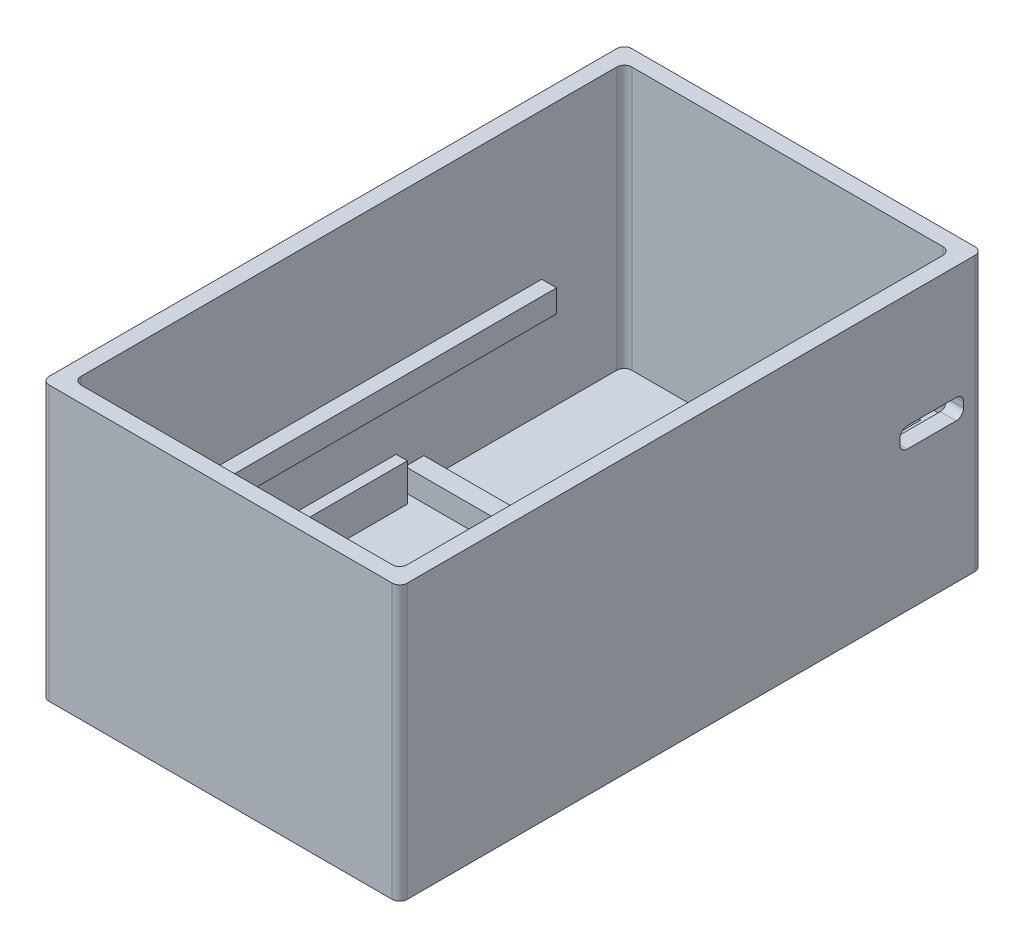
SolidWorks part; units mm, degrees
ref_plane "Front Plane" through (0, 0, 0) normal (0, 0, 1) x (1, 0, 0)
ref_plane "Top Plane" through (0, 0, 0) normal (0, 1, 0) x (1, 0, 0)
ref_plane "Right Plane" through (0, 0, 0) normal (1, 0, 0) x (0, 0, -1)
sketch "PCB Dimensions" plane through (0, 0, 0) normal (0, 1, 0) x (1, 0, 0)
  line L0 (0, 0) -> (-3.5355, 3.5355)
  line L1 (0, 0) -> (40.6457, 0)
  line L2 (0, 0) -> (0, -70.5657)
  line L3 (0, -70.5657) -> (40.6457, -70.5657)
  line L4 (40.6457, 0) -> (40.6457, -70.5657)
  line L5 (40.6457, -70.5657) -> (44.1812, -74.1012)
  line L6 (40.6457, 0) -> (44.1812, 3.5355)
  line L11 (0, -70.5657) -> (-3.5355, -74.1012)
  line L12 (44.1812, -74.1012) -> (-3.5355, -74.1012)
  line L13 (44.1812, -74.1012) -> (44.1812, 3.5355)
  line L14 (44.1812, 3.5355) -> (-3.5355, 3.5355)
  line L15 (-3.5355, -74.1012) -> (-3.5355, 3.5355)
extrude "Boss-Extrude3" add sketch "PCB Dimensions" along normal blind 1.5 contours L14 L15 L12 L13
sketch "Sketch5" plane through (0, 1.5, 0) normal (0, 1, 0) x (1, 0, 0)
  line L0 (-3.5355, 3.5355) -> (-1.4142, 1.4142)
  line L1 (-3.5355, 3.5355) -> (44.1812, 3.5355)
  line L2 (-3.5355, 3.5355) -> (-3.5355, -74.1012)
  line L7 (-3.5355, -74.1012) -> (44.1812, -74.1012)
  line L8 (44.1812, 3.5355) -> (44.1812, -74.1012)
  line L9 (44.1812, -74.1012) -> (42.0599, -71.9799)
  line L11 (-1.4142, 1.4142) -> (42.0599, 1.4142)
  line L12 (-1.4142, 1.4142) -> (-1.4142, -71.9799)
  line L13 (-1.4142, -71.9799) -> (42.0599, -71.9799)
  line L14 (42.0599, 1.4142) -> (42.0599, -71.9799)
extrude "Boss-Extrude5" add sketch "Sketch5" along normal blind 35 contours L14 L13 | L2 L7 L8 L1 region at (20.3228, 1.5, 35.2828)
fillet "Fillet1" radius 1 8 edges at (42.0599, 19, 71.9799) (-3.5355, 18.25, 74.1012) (44.1812, 18.25, 74.1012) (44.1812, 18.25, -3.5355) (-3.5355, 18.25, -3.5355) (-1.4142, 19, 71.9799) (42.0599, 19, -1.4142) (-1.4142, 19, -1.4142)
sketch "Sketch9" plane through (0, 1.5, 0) normal (0, 1, 0) x (1, 0, 0)
  line L3 (0.0799, -70.9799) -> (-1.8581, -70.9799)
  line L9 (0.0799, -28.9799) -> (-1.8581, -28.9799)
  line L10 (-1.8581, -70.9799) -> (-1.8581, -28.9799)
  line L15 (42.5038, -70.9799) -> (42.5038, -28.9799)
  line L16 (40.5658, -28.9799) -> (42.5038, -28.9799)
  line L18 (40.5658, -70.9799) -> (42.5038, -70.9799)
  line L21 (0.0799, -28.9799) -> (0.0799, -70.9799)
  line L23 (40.5658, -28.9799) -> (40.5658, -70.9799)
  point P5 (0, 0)
sketch "Sketch7" plane through (0, 1.5, 0) normal (0, 1, 0) x (1, 0, 0)
  line L3 (-0.4992, 0.4992) -> (41.1449, 0.4992)
  line L4 (-0.4992, 0.4992) -> (-0.4992, -71.0649)
  line L5 (-0.4992, -71.0649) -> (41.1449, -71.0649)
  line L6 (41.1449, 0.4992) -> (41.1449, -71.0649)
  point P18 (0, 0)
extrude "Boss-Extrude6" add sketch "Sketch9" along normal blind 5 contours L21 L3 L10 L9 | L23 L18 L15 L16
sketch "Sketch14" plane through (0, 1.5, 0) normal (0, 1, 0) x (1, 0, 0)
  line L2 (-1.4142, -27.7799) -> (13.5858, -27.7799)
  line L3 (-1.4142, -27.7799) -> (-1.4142, -25.2799)
  line L4 (-1.4142, -25.2799) -> (13.5858, -25.2799)
  line L5 (13.5858, -27.7799) -> (13.5858, -25.2799)
  line L6 (27.0599, -27.7799) -> (27.0599, -25.2799)
  line L7 (42.0599, -25.2799) -> (27.0599, -25.2799)
  line L8 (42.0599, -27.7799) -> (42.0599, -25.2799)
  line L9 (42.0599, -27.7799) -> (27.0599, -27.7799)
extrude "Boss-Extrude7" add sketch "Sketch14" along normal blind 3
sketch "Sketch15" plane through (44.1812, 0, 0) normal (1, 0, 0) x (0, 0, -1)
  line L1 (-73.1012, 36.5) -> (-73.1012, 0) construction
  line L3 (2.5355, 0) -> (2.5355, 36.5) construction
  line L4 (-73.1012, 14) -> (2.5355, 14)
  line L5 (-73.1012, 14) -> (-73.1012, 17)
  line L6 (-73.1012, 17) -> (2.5355, 17)
  line L7 (2.5355, 14) -> (2.5355, 17)
  line M8 (-73.1012, 36.5) -> (-73.1012, 0)
  line M10 (2.5355, 0) -> (2.5355, 36.5)
extrude "Boss-Extrude8" add sketch "Sketch15" against normal blind 46 contours L6 L4 M8 M10 region at (44.1812, 15.5, 35.2828)
sketch "Sketch17" plane through (0, 17, 0) normal (0, 1, 0) x (1, 0, 0)
  line L3 (40.0842, -63.5437) -> (0.5614, -63.5437)
  line L4 (40.0842, -63.5437) -> (40.0842, -0.5614)
  line L5 (40.0842, -0.5614) -> (0.5614, -0.5614)
  line L6 (0.5614, -63.5437) -> (0.5614, -0.5614)
extrude "Cut-Extrude1" cut sketch "Sketch17" against normal blind 3 contours L5 L6 L3 L4
sketch "Sketch18" plane through (0, 17, 0) normal (0, 1, 0) x (1, 0, 0)
  line L0 (-1.4142, -70.9799) -> (-1.4142, 0.4142) construction
  line L1 (-1.4142, -9.5858) -> (28.5858, -9.5858)
  line L4 (28.5858, -9.5858) -> (28.5858, 1.4142)
  line L5 (-0.4142, 1.4142) -> (41.0599, 1.4142) construction
  line L6 (-0.4142, 1.4142) -> (28.5858, 1.4142)
  line L7 (-1.4142, 0.4142) -> (-1.4142, -9.5858)
  arc A0 (-1.4142, 0.4142) -> (-0.4142, 1.4142) centre (-0.4142, 0.4142) cw
extrude "Cut-Extrude2" cut sketch "Sketch18" against normal blind 3
sketch "Sketch19" plane through (44.1812, 0, 0) normal (1, 0, 0) x (0, 0, -1)
  line L0 (2.5355, 0) -> (2.5355, 17)
  line L1 (2.5355, 0) -> (2.5355, 36.5) construction
  line L3 (1.0355, 18.65) -> (-7.4645, 18.65)
  line L4 (1.0355, 18.65) -> (1.0355, 21.35)
  line L9 (1.0355, 21.35) -> (-7.4645, 21.35)
  line L10 (-7.4645, 18.65) -> (-7.4645, 21.35)
  point P5 (0, 0)
extrude "Cut-Extrude3" cut sketch "Sketch19" against normal blind 3 contours L10 L3 L4 L9 region at (44.1812, 20, 3.2145)
fillet "Fillet2" radius 1 4 edges at (43.1205, 18.65, 7.4645) (43.0123, 18.65, -1.0355) (43.0123, 21.35, -1.0355) (43.1205, 21.35, 7.4645)
